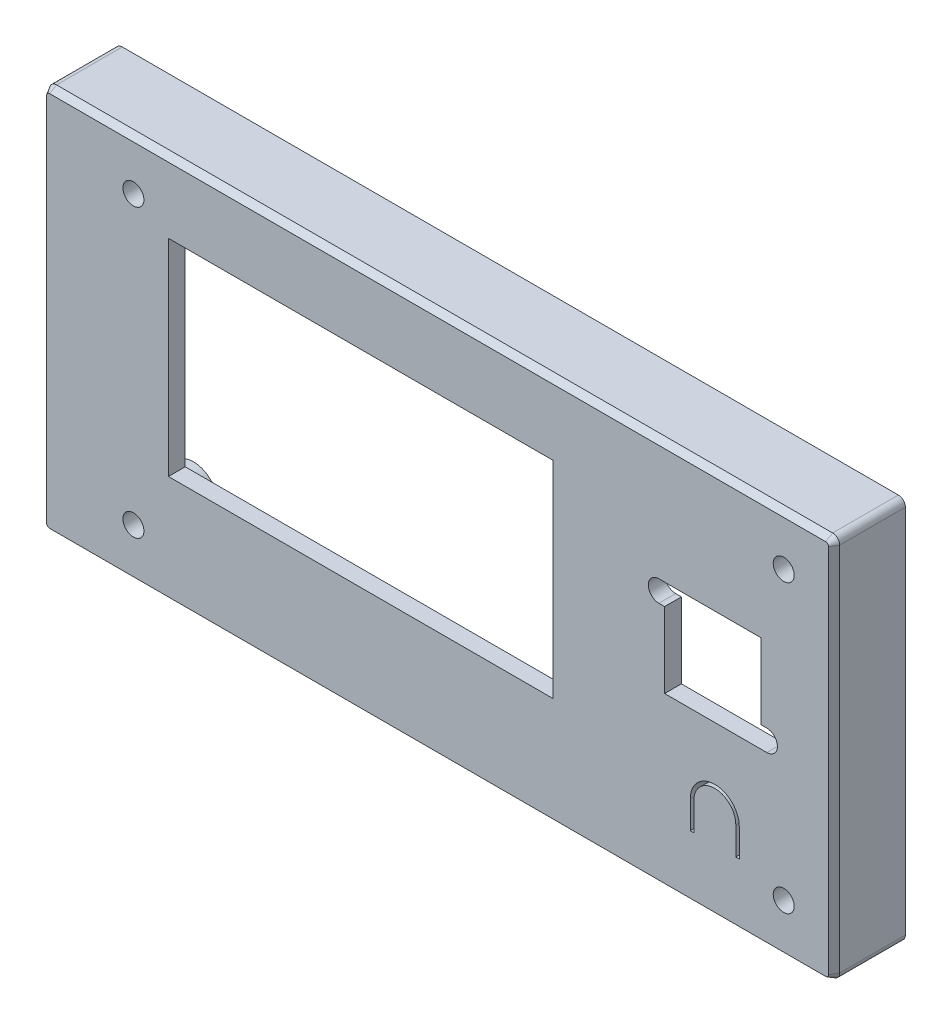
SolidWorks part; units mm, degrees
ref_plane "정면" through (0, 0, 0) normal (0, 0, 1) x (1, 0, 0)
ref_plane "윗면" through (0, 0, 0) normal (0, 1, 0) x (1, 0, 0)
ref_plane "우측면" through (0, 0, 0) normal (1, 0, 0) x (0, 0, -1)
ref_plane "평면1" through (0, 0, 96.6864) normal (0, 0, 1) x (1, 0, 0)
sketch "스케치1" plane through (0, 0, 96.6864) normal (0, 0, 1) x (1, 0, 0)
  line L1 (-76.6031, 28.3954) -> (36.3859, 28.3954)
  line L2 (-76.6031, 28.3954) -> (-76.6031, -26.6046)
  line L3 (-76.6031, -26.6046) -> (36.3859, -26.6046)
  line L4 (36.3859, 28.3954) -> (36.3859, -26.6046)
extrude "돌출-얇게1" add sketch "스케치1" along normal blind 8 thin
sketch "스케치2" plane through (0, 0, 104.6864) normal (0, 0, 1) x (1, 0, 0)
  line L0 (-31.9046, -22.6046) -> (-31.9046, -11.1046)
  line L1 (-67.2141, -22.6046) -> (29.3859, -22.6046) construction
  line L2 (-31.2617, 24.3954) -> (-31.2617, 18.3954)
  line L3 (29.3859, 24.3954) -> (-72.6031, 24.3954) construction
  line L4 (-72.6031, 1.8396) -> (-58.6031, 1.8396)
  line L5 (-72.6031, 24.3954) -> (-72.6031, -17.2156) construction
  line L6 (32.3859, 2.2641) -> (-3.6141, 2.2641)
  line L7 (32.3859, -19.6046) -> (32.3859, 21.3954) construction
  line L8 (11.5341, 8.2649) -> (11.5341, 11.2942)
  line L9 (-58.6031, 18.3954) -> (-3.6141, 18.3954)
  line L10 (-58.6031, 18.3954) -> (-58.6031, -11.1046)
  line L11 (-58.6031, -11.1046) -> (-3.6141, -11.1046)
  line L12 (-3.6141, 18.3954) -> (-3.6141, -11.1046)
  line L13 (12.3533, -2.5058) -> (26.1533, -2.5058)
  line L14 (12.3533, -2.5058) -> (12.3533, 11.2942)
  line L15 (12.3533, 11.2942) -> (26.1533, 11.2942)
  line L16 (26.1533, -2.5058) -> (26.1533, 11.2942)
  line L17 (12.3533, -2.5058) -> (26.1533, 11.2942) construction
  line L18 (12.3533, 11.2942) -> (26.1533, -2.5058) construction
  line L19 (26.9724, 0.5234) -> (24.4304, 0.5234)
  line L20 (26.9724, 0.5234) -> (26.9724, -2.5058)
  line L21 (26.9724, -2.5058) -> (24.4304, -2.5058)
  line L22 (24.4304, 0.5234) -> (24.4304, -2.5058)
  line L23 (11.5341, 8.2649) -> (14.0761, 8.2649)
  line L24 (14.0761, 8.2649) -> (14.0761, 11.2942)
  line L25 (11.5341, 11.2942) -> (14.0761, 11.2942)
  line L27 (-76.6031, 28.3954) -> (36.3859, 28.3954)
  line L28 (-76.6031, 28.3954) -> (-76.6031, -26.6046)
  line L29 (-76.6031, -26.6046) -> (36.3859, -26.6046)
  line L30 (36.3859, 28.3954) -> (36.3859, -26.6046)
  line L31 (16.0335, -13.6638) -> (16.0335, -17.6638)
  line L32 (16.0335, -17.6638) -> (16.5335, -17.6638)
  line L33 (16.5335, -17.6638) -> (16.5335, -13.6638)
  line L34 (16.5335, -10.9138) -> (16.5335, -16.4138) construction
  line L35 (22.5335, -13.6638) -> (22.5335, -17.6638)
  line L36 (22.5335, -17.6638) -> (23.0335, -17.6638)
  line L37 (23.0335, -17.6638) -> (23.0335, -13.6638)
  circle A0 centre (26.9724, -0.9912) radius 1.5146
  circle A1 centre (11.5341, 9.7796) radius 1.5146
  arc A3 (16.0335, -13.6638) -> (23.0335, -13.6638) centre (19.5335, -13.6638) cw
  arc A4 (16.5335, -13.6638) -> (22.5335, -13.6638) centre (19.5335, -13.6638) cw
  circle A5 centre (-63.6141, -19.6046) radius 1.5
  circle A6 centre (-63.6141, 21.3954) radius 1.5
  circle A7 centre (29.3859, 21.3954) radius 1.5
  circle A8 centre (29.3859, -19.6046) radius 1.5
  point P20 (19.2533, 4.3942)
  point P42 (19.2533, 4.3942)
  point P52 (19.5335, -13.6638)
  dimension "D1" = 11.5
  dimension "D2" = 6
  dimension "D3" = 14
  dimension "D4" = 36
  dimension "D5" = 13.8
  dimension "D6" = 13.8
  dimension "D8" = 4
  dimension "D9" = 4
  dimension "D7" = 2
extrude "보스-돌출1" add sketch "스케치2" along normal blind 2.4
sketch "스케치3" plane through (0, 0, 104.6864) normal (0, 0, -1) x (-1, 0, 0)
  line L1 (-22.5335, -13.6638) -> (-16.5335, -13.6638)
  line L2 (-22.5335, -13.6638) -> (-22.5335, -17.6638)
  line L3 (-22.5335, -17.6638) -> (-16.5335, -17.6638)
  line L4 (-16.5335, -13.6638) -> (-16.5335, -17.6638)
  circle A0 centre (-19.5335, -13.6638) radius 3
  arc M21 (-16.5335, -13.6638) -> (-22.5335, -13.6638) centre (-19.5335, -13.6638) ccw
  line M22 (-22.5335, -13.6638) -> (-22.5335, -17.6638)
  line M28 (-16.5335, -17.6638) -> (-16.5335, -13.6638)
extrude "컷-돌출1" cut sketch "스케치3" against normal blind 1.4 contours L1 M21 | L1 A0 | A0 L3 M22 M28
chamfer "모따기1" distance 1.4 angle 45 1 edges at (19.5335, -17.6638, 106.0864)
sketch "스케치4" plane through (0, 0, 104.6864) normal (0, 0, -1) x (-1, 0, 0)
  circle A0 centre (63.6141, 21.3954) radius 1.5
  circle A1 centre (63.6141, -19.6046) radius 1.5
  circle A2 centre (-29.3859, -19.6046) radius 1.5
  circle A3 centre (-29.3859, 21.3954) radius 1.5
  circle A4 centre (-29.3859, 21.3954) radius 3.51
  circle A5 centre (-29.3859, -19.6046) radius 3.51
  circle A6 centre (63.6141, -19.6046) radius 3.51
  circle A7 centre (63.6141, 21.3954) radius 3.51
extrude "보스-돌출2" add sketch "스케치4" along normal blind 6.2
fillet "필렛1" radius 1 4 edges at (-76.6031, 28.3954, 101.8864) (36.3859, 28.3954, 101.8864) (36.3859, -26.6046, 101.8864) (-76.6031, -26.6046, 101.8864)
chamfer "모따기2" distance 1 angle 30 8 edges at (-20.1086, -26.6046, 107.0864) (36.093, -26.3117, 107.0864) (-76.3102, -26.3117, 107.0864) (36.3859, 0.8954, 107.0864) (-76.6031, 0.8954, 107.0864) (36.093, 28.1025, 107.0864) (-76.3102, 28.1025, 107.0864) (-20.1086, 28.3954, 107.0864)
